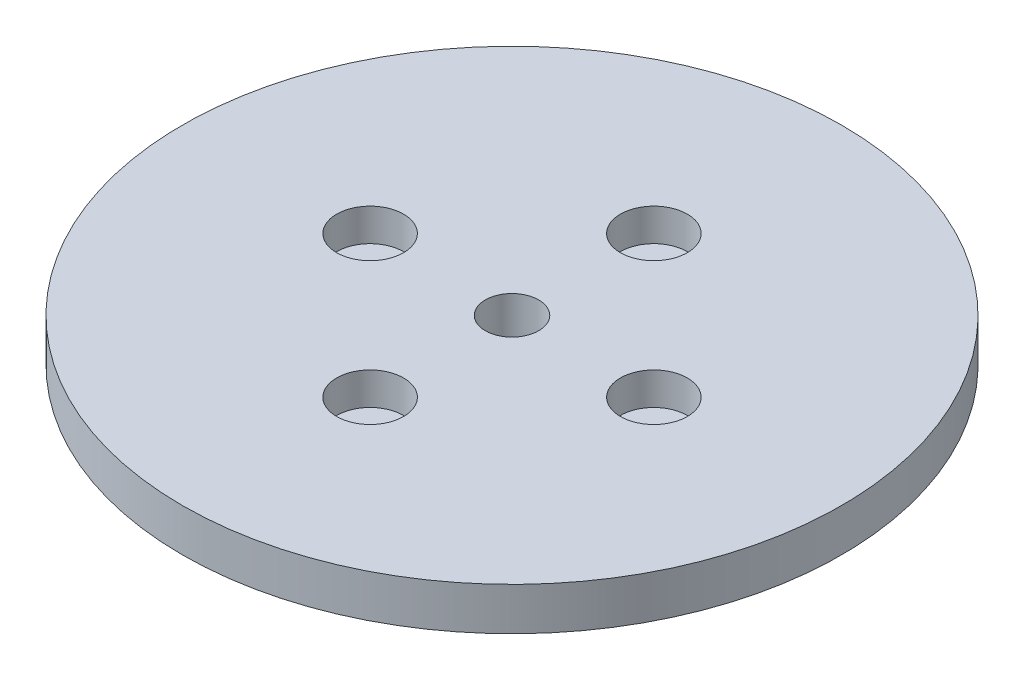
SolidWorks part; units mm, degrees
ref_plane "Front Plane" through (0, 0, 0) normal (0, 0, 1) x (1, 0, 0)
ref_plane "Top Plane" through (0, 0, 0) normal (0, 1, 0) x (1, 0, 0)
ref_plane "Right Plane" through (0, 0, 0) normal (1, 0, 0) x (0, 0, -1)
sketch "Sketch1" plane through (0, 0, 0) normal (0, 1, 0) x (1, 0, 0)
  circle A0 centre (0, 0) radius 92.5
  dimension "FLANGE_OD" = 185
extrude "Boss-Extrude1" add sketch "Sketch1" along normal blind 12
sketch "Sketch2" plane through (0, 0, 0) normal (0, 1, 0) x (1, 0, 0)
  circle A0 centre (0, 0) radius 7.5
  dimension "BORE_D" = 15
extrude "Cut-Extrude1" cut sketch "Sketch2" along normal through all
sketch "Sketch3" plane through (0, 12, 0) normal (0, 1, 0) x (1, 0, 0)
  circle A0 centre (0, 0) radius 39.8194 construction
  circle A1 centre (-39.8194, 0) radius 9.3884
  dimension "BOLT_D" = 18.7767
  dimension "BOLT_PCD" = 79.6387
extrude "Cut-Extrude2" cut sketch "Sketch3" against normal blind 9.1272
pattern_circular "CirPattern1" count 4 over 360 about axis through (0, 0, 0) along (0, 1, 0) of "Cut-Extrude2"
